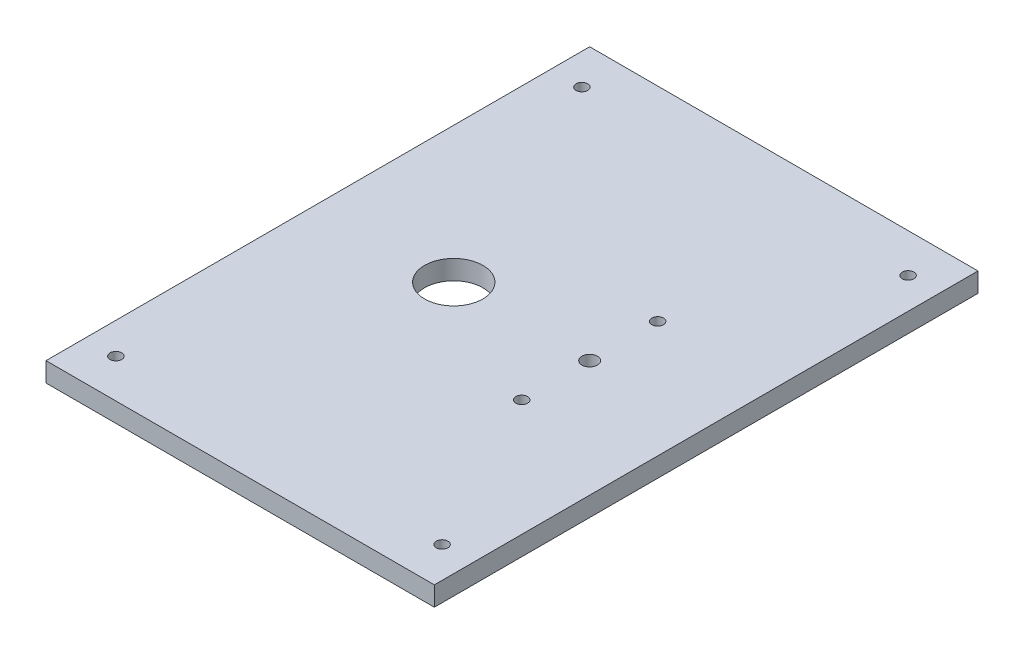
SolidWorks part; units mm, degrees
ref_plane "Front Plane" through (0, 0, 0) normal (0, 0, 1) x (1, 0, 0)
ref_plane "Top Plane" through (0, 0, 0) normal (0, 1, 0) x (1, 0, 0)
ref_plane "Right Plane" through (0, 0, 0) normal (1, 0, 0) x (0, 0, -1)
sketch "Sketch1" plane through (0, 0, 0) normal (0, 1, 0) x (1, 0, 0)
  line L0 (57.4631, 0) -> (-59.6494, 0) construction
  line L1 (-50, -70) -> (50, -70)
  line L2 (-50, -70) -> (-50, 70)
  line L3 (-50, 70) -> (50, 70)
  line L4 (50, -70) -> (50, 70)
  line L5 (-50, -70) -> (50, 70) construction
  line L6 (-50, 70) -> (50, -70) construction
  circle A0 centre (-15, 0) radius 7.5
  circle A1 centre (20, 0) radius 2
  circle A2 centre (20, -17.5) radius 1.5
  circle A3 centre (20, 17.5) radius 1.5
  point P0 (0, 0)
  point P16 (0, 0)
  dimension "D3" = 30
  dimension "D4" = 4
  dimension "D6" = 3
  dimension "D9" = 15
  dimension "D1" = 140
  dimension "D2" = 100
  dimension "D5" = 35
  dimension "D8" = 17.5
extrude "Boss-Extrude1" add sketch "Sketch1" along normal blind 5
hole_wizard "Ø3.0 (3) Diameter Hole1" positions "Sketch3" profile "Sketch2" hole size "Ø3.0" standard "Ansi Metric" end condition through all
sketch "Sketch3" plane through (0, 5, 0) normal (0, 1, 0) x (-1, 0, 0)
  line L0 (76.9077, 0) -> (-75.5177, 0) construction
  line L2 (-50, 70) -> (-50, -70) construction
  line L3 (50, -70) -> (50, 70) construction
  line L4 (-50, -70) -> (50, -70) construction
  point P1 (-42, 60)
  point P3 (42, 60)
  point P5 (42, -60)
  point P7 (-42, -60)
  dimension "D1" = 120
  dimension "D2" = 8
  dimension "D3" = 8
  dimension "D4" = 10
  dimension "D5" = 84
sketch "Sketch2" plane through (42, 5, 60) normal (1, 0, 0) x (0, 0, 1)
  line L0 (0, 0) -> (0, 5)
  line L1 (0, 5) -> (1.5, 5)
  line L2 (1.5, 5) -> (1.5, 0)
  line L5 (1.5, 0) -> (0, 0)
  line L11 (0, -6.35) -> (0, 107.95) construction
  dimension "Thru Hole Dia." = 3
  dimension "Thru Hole Depth" = 5
ref_axis "Front Hole Axis" through (-42, 0, 60) along (0, 1, 0)
ref_plane "Front Hole Plane" through (-42, 0, 0) normal (1, 0, 0) x (0, 0, -1)
